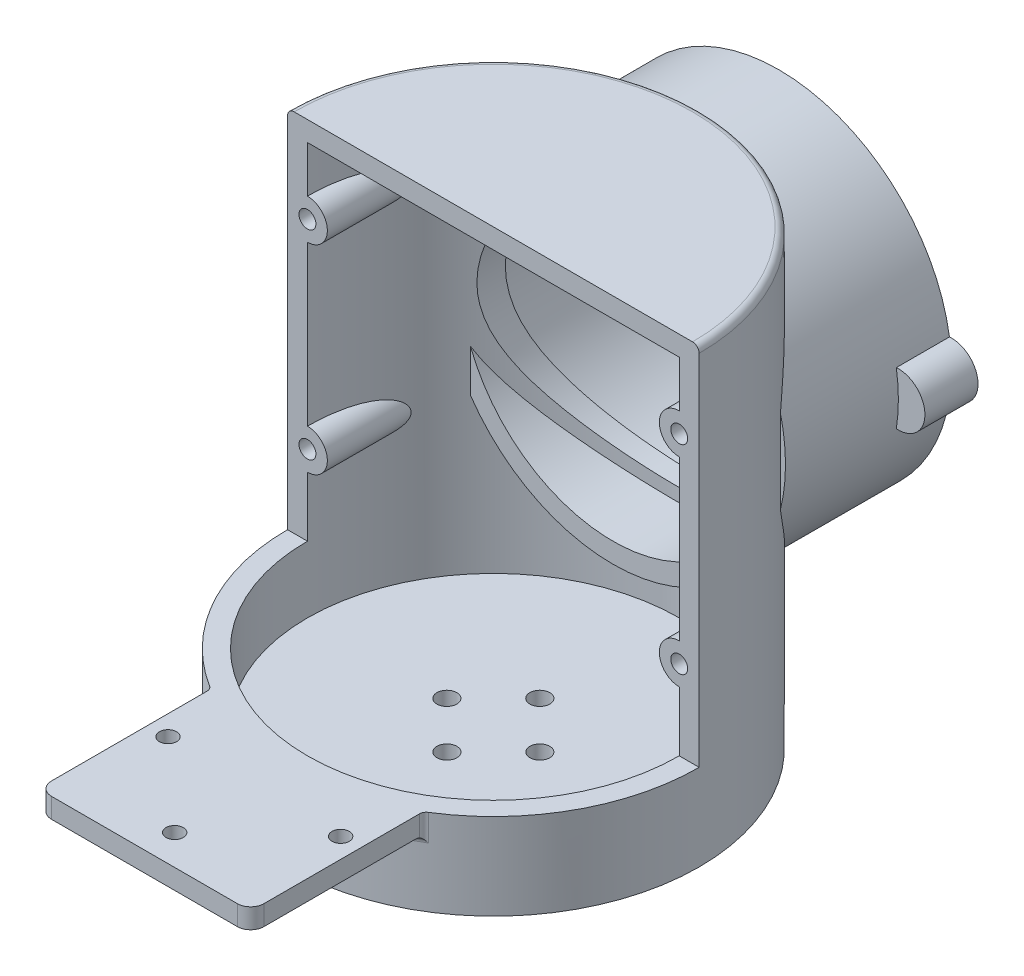
SolidWorks part; units mm, degrees
ref_plane "Спереди" through (0, 0, 0) normal (0, 0, 1) x (1, 0, 0)
ref_plane "Сверху" through (0, 0, 0) normal (0, 1, 0) x (1, 0, 0)
ref_plane "Справа" through (0, 0, 0) normal (1, 0, 0) x (0, 0, -1)
sketch "Эскиз3" plane through (0, 0, 0) normal (1, 0, 0) x (0, 0, -1)
  line L0 (0, 68.2882) -> (0, 0) construction
  line L1 (0, 0) -> (31, 0)
  line L2 (31, 0) -> (31, 68)
  line L3 (31, 68) -> (0, 68)
  line L4 (0, 68) -> (0, 65)
  line L5 (0, 65) -> (28, 65)
  line L6 (28, 65) -> (28, 3)
  line L7 (28, 3) -> (0, 3)
  line L8 (0, 3) -> (0, 0)
  dimension "D1" = 62
  dimension "D2" = 68
  dimension "D3" = 3
  dimension "D4" = 3
  dimension "D5" = 3
revolve "Повернуть2" add sketch "Эскиз3" angle 360 about L0
sketch "Эскиз4" plane through (0, 68, 0) normal (0, 1, 0) x (1, 0, 0)
  line L0 (-31, 0) -> (31, 0)
  circle A0 centre (0, 0) radius 31 construction
  arc A1 (31, 0) -> (-31, 0) centre (0, 0) cw
extrude "Вырез-Вытянуть1" cut sketch "Эскиз4" against normal blind 55
sketch "Эскиз5" plane through (0, 0, 0) normal (0, -1, 0) x (1, 0, 0)
  circle A0 centre (0, 0) radius 19.5
  circle A1 centre (0, 0) radius 29.5
  dimension "D1" = 59
  dimension "D2" = 39
sketch "Эскиз6" plane through (0, 0, 0) normal (0, -1, 0) x (1, 0, 0)
  circle A0 centre (7, 0) radius 1.5
  dimension "D1" = 3
  dimension "D2" = 7
extrude "Вырез-Вытянуть3" cut sketch "Эскиз6" against normal up to surface (3 mm away) up to face at (0, 3, 28)
pattern_circular "Круговой массив1" count 4 over 360 about axis through (0, 68.2882, 0) along (0, 1, 0) of "Вырез-Вытянуть3"
sketch "Эскиз7" plane through (0, 0, 0) normal (0, 0, 1) x (1, 0, 0)
  circle A0 centre (0, 41) radius 23
  circle A1 centre (0, 41) radius 26
  dimension "D1" = 52
  dimension "D2" = 46
  dimension "D3" = 41
extrude "Бобышка-Вытянуть1" add sketch "Эскиз7" against normal blind 25 from offset 18 offset against normal yes
sketch "Эскиз8" plane through (0, 0, -43) normal (0, 0, -1) x (-1, 0, 0)
  circle A0 centre (0, 41) radius 21
  dimension "D1" = 42
  dimension "D2" = 41
extrude "Вырез-Вытянуть4" cut sketch "Эскиз8" against normal blind 25
sketch "Эскиз9" plane through (0, 13, 0) normal (0, 1, 0) x (1, 0, 0)
  line L0 (-16, -26.5518) -> (-16, -52.5518)
  line L1 (-16, -52.5518) -> (16, -52.5518)
  line L2 (16, -52.5518) -> (16, -26.5518)
  line L3 (0, 0) -> (0, -52.5518) construction
  arc A0 (16, -26.5518) -> (-16, -26.5518) centre (0, 0) cw
  arc A1 (-31, 0) -> (31, 0) centre (0, 0) ccw construction
  dimension "D1" = 26
  dimension "D2" = 32
extrude "Бобышка-Вытянуть2" add sketch "Эскиз9" against normal blind 3
fillet "Скругление1" radius 2 2 edges at (16, 11.5, 52.5518) (-16, 11.5, 52.5518)
fillet "Скругление2" radius 1 4 edges at (16, 11.5, 26.5518) (0, 10, 31) (-16, 11.5, 26.5518) (0, 68, -31)
sketch "Эскиз11" plane through (0, 0, 0) normal (0, 0, 1) x (1, 0, 0)
  line L0 (-28, 65) -> (-28, 13) construction
  line L1 (28, 13) -> (28, 65) construction
  line L3 (-28, 25) -> (28, 25) construction
  line L4 (-28, 25) -> (-28, 55) construction
  line L5 (-28, 55) -> (28, 55) construction
  line L6 (28, 25) -> (28, 55) construction
  circle A0 centre (-28, 55) radius 3
  circle A1 centre (-28, 25) radius 3
  circle A2 centre (28, 25) radius 3
  circle A3 centre (28, 55) radius 3
  point P12 (0, 25)
  point P15 (28, 40)
  dimension "D1" = 6
  dimension "D2" = 6
  dimension "D3" = 6
  dimension "D4" = 6
  dimension "D5" = 30
  dimension "D6" = 40
extrude "Бобышка-Вытянуть3" add sketch "Эскиз11" against normal up to surface (12.6095 mm away) up to face at (20.9954, 40.5593, -18.5255)
hole_wizard "Сверло под метчик  спиральное M2.52" positions "Эскиз15" profile "Эскиз16" hole size "M2.5x0.45" standard "Ansi Metric"
sketch "Эскиз15" plane through (0, 0, 0) normal (0, 0, 1) x (1, 0, 0)
  point P0 (-28, 55)
  point P3 (28, 55)
  point P6 (28, 25)
  point P9 (-28, 25)
sketch "Эскиз16" plane through (-28, 55, 0) normal (1, 0, 0) x (0, -1, 0)
  line L0 (0, 0) -> (0, 5.7661)
  line L1 (0, 5.7661) -> (1.275, 5)
  line L2 (1.275, 5) -> (1.275, 0)
  line L5 (1.275, 0) -> (0, 0)
  line L10 (0, 5.7661) -> (-1.275, 5) construction
  line L11 (0, -6.35) -> (0, 107.95) construction
  dimension "Диаметр отверстия" = 2.55
  dimension "Глубина отверстия" = 5
  dimension "Угол заточки сверла" = 118
sketch "Эскиз17" plane through (0, 13, 0) normal (0, 1, 0) x (1, 0, 0)
  circle A0 centre (-13, -36) radius 1.3
  circle A1 centre (0, -48) radius 1.3
  circle A2 centre (13, -36) radius 1.3
  dimension "D1" = 2.6
  dimension "D2" = 36
  dimension "D3" = 12
  dimension "D4" = 13
  dimension "D5" = 26
extrude "Вырез-Вытянуть5" cut sketch "Эскиз17" against normal up to surface (3 mm away) up to face at (0, 10, 44.4581)
sketch "Эскиз18" plane through (0, 0, -43) normal (0, 0, -1) x (-1, 0, 0)
  circle A0 centre (0, 41) radius 26 construction
  arc A1 (-25.6923, 44.9881) -> (-25.6923, 37.0119) centre (0, 41) ccw
  arc A3 (-3.9881, 15.3077) -> (3.9881, 15.3077) centre (0, 15) ccw
  arc A4 (25.6923, 37.0119) -> (25.6923, 44.9881) centre (26, 41) ccw
  arc A5 (-25.6923, 44.9881) -> (-25.6923, 37.0119) centre (-26, 41) ccw
  arc A6 (-3.9881, 15.3077) -> (3.9881, 15.3077) centre (0, 41) ccw
  arc A7 (25.6923, 37.0119) -> (25.6923, 44.9881) centre (0, 41) ccw
  dimension "D1" = 52
  dimension "D2" = 8
  dimension "D3" = 26
extrude "Бобышка-Вытянуть4" add sketch "Эскиз18" against normal blind 8
hole_wizard "Отверстие с зазором M21" positions "Эскиз19" profile "Эскиз21" hole size "M2" standard "Ansi Metric"
sketch "Эскиз19" plane through (0, 0, -43) normal (0, 0, -1) x (-1, 0, 0)
  point P0 (-26, 41)
  point P3 (0, 15)
  point P6 (26, 41)
sketch "Эскиз21" plane through (26, 41, -43) normal (1, 0, 0) x (0, 1, 0)
  line L0 (0, 0) -> (0, 5.721)
  line L1 (0, 5.721) -> (1.2, 5)
  line L2 (1.2, 5) -> (1.2, 0)
  line L5 (1.2, 0) -> (0, 0)
  line L10 (0, 5.721) -> (-1.2, 5) construction
  line L11 (0, -6.35) -> (0, 107.95) construction
  dimension "Диаметр отверстия" = 2.4
  dimension "Глубина отверстия" = 5
  dimension "Угол заточки сверла" = 118
